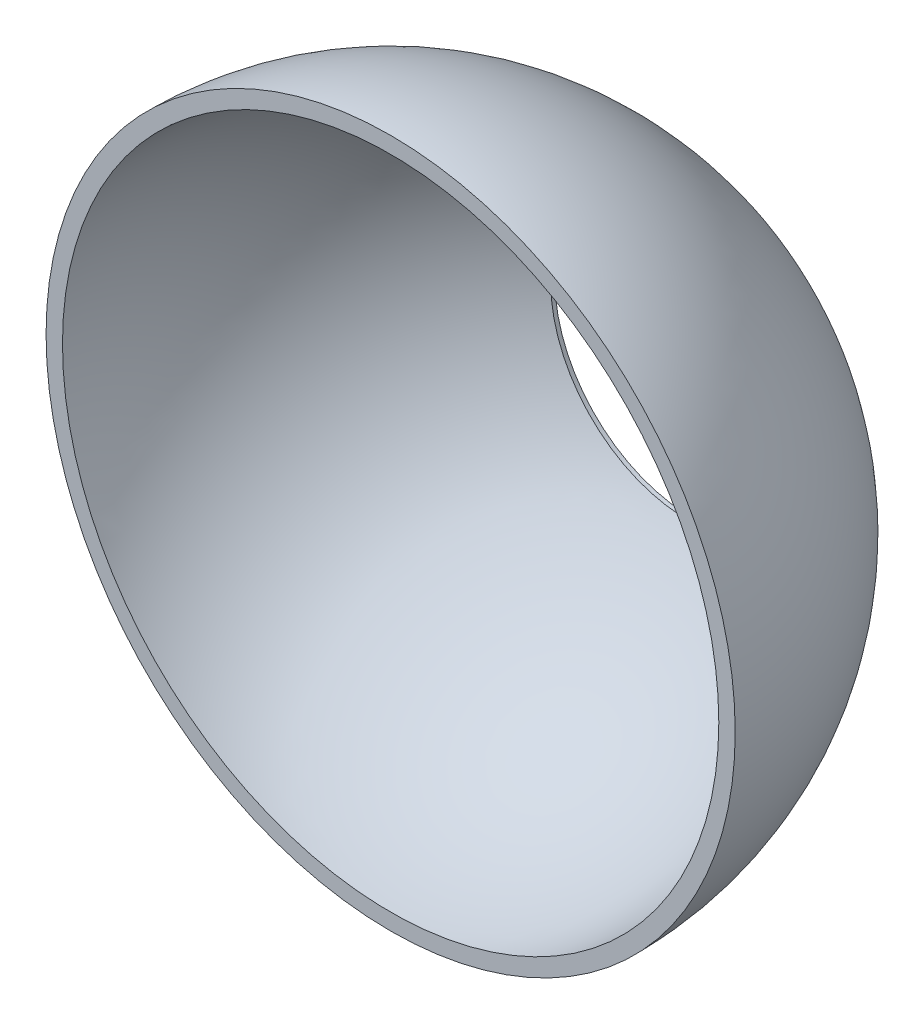
SolidWorks part; units mm, degrees
ref_plane "Front Plane" through (0, 0, 0) normal (0, 0, 1) x (1, 0, 0)
ref_plane "Top Plane" through (0, 0, 0) normal (0, 1, 0) x (1, 0, 0)
ref_plane "Right Plane" through (0, 0, 0) normal (1, 0, 0) x (0, 0, -1)
ref_axis "Polar Axis" through (0, 0, -14.3) along (0, 0, 1)
ref_axis "Solar Axis" through (-14.3, 0, 0) along (1, 0, 0)
sketch "Sketch2" plane through (0, 0, 0) normal (0, 1, 0) x (1, 0, 0)
  line L0 (10, 0) -> (10.5, 0)
  line L1 (0, 0) -> (0, 10.25) construction
  line L3 (4.2, 9.0752) -> (4.2, 9.2)
  line L4 (5.0606, 9.2) -> (4.2, 9.2)
  arc A0 (10.5, 0) -> (5.0606, 9.2) centre (0, 0) ccw
  arc A1 (10, 0) -> (4.2, 9.0752) centre (0, 0) ccw
  dimension "D1" = 21
  dimension "D2" = 0.5
  dimension "D3" = 4.2
  dimension "D4" = 9.2
revolve "Main Body" add sketch "Sketch2" angle 360 about L1
